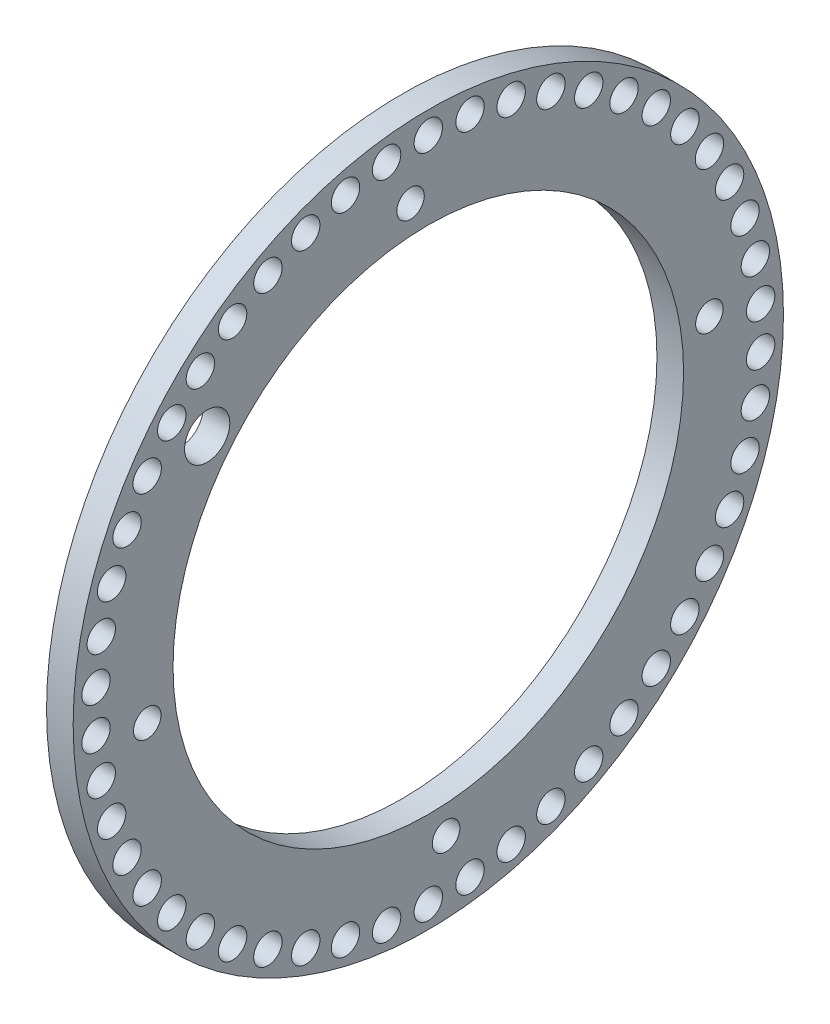
SolidWorks part; units mm, degrees
material "AISI 304"
ref_plane "Front Plane" through (0, 0, 0) normal (0, 0, 1) x (1, 0, 0)
ref_plane "Top Plane" through (0, 0, 0) normal (0, 1, 0) x (1, 0, 0)
ref_plane "Right Plane" through (0, 0, 0) normal (1, 0, 0) x (0, 0, -1)
sketch "Sketch1" plane through (0, 0, 0) normal (1, 0, 0) x (0, 0, -1)
  line L0 (0, 0) -> (0, 40) construction
  line L66 (0, 0) -> (40, 0) construction
  line L67 (0, 0) -> (-40, 0) construction
  line L72 (0, 0) -> (0, -40) construction
  line L73 (0, 0) -> (-28.8942, 23.9034) construction
  line L74 (-22.1523, 18.3259) -> (-19.9302, 21.0119) construction
  line L76 (-27.6614, 22.8835) -> (-26.156, 24.7033) construction
  circle A3 centre (0, 0) radius 40
  circle A24 centre (0, 37.5) radius 1.6
  circle A25 centre (0, 0) radius 28.75
  circle A26 centre (4.7, 37.2043) radius 1.6
  circle A27 centre (9.3259, 36.3219) radius 1.6
  circle A28 centre (13.8047, 34.8666) radius 1.6
  circle A29 centre (18.0658, 32.8615) radius 1.6
  circle A30 centre (22.0419, 30.3381) radius 1.6
  circle A31 centre (25.6705, 27.3363) radius 1.6
  circle A32 centre (28.8942, 23.9034) radius 1.6
  circle A33 centre (31.6623, 20.0935) radius 1.6
  circle A34 centre (33.931, 15.9667) radius 1.6
  circle A35 centre (35.6646, 11.5881) radius 1.6
  circle A36 centre (36.8358, 7.0268) radius 1.6
  circle A37 centre (37.426, 2.3546) radius 1.6
  circle A38 centre (37.426, -2.3546) radius 1.6
  circle A39 centre (36.8358, -7.0268) radius 1.6
  circle A40 centre (35.6646, -11.5881) radius 1.6
  circle A41 centre (33.931, -15.9667) radius 1.6
  circle A42 centre (31.6623, -20.0935) radius 1.6
  circle A43 centre (28.8942, -23.9034) radius 1.6
  circle A44 centre (25.6705, -27.3363) radius 1.6
  circle A45 centre (22.0419, -30.3381) radius 1.6
  circle A46 centre (18.0658, -32.8615) radius 1.6
  circle A47 centre (13.8047, -34.8666) radius 1.6
  circle A48 centre (9.3259, -36.3219) radius 1.6
  circle A49 centre (4.7, -37.2043) radius 1.6
  circle A50 centre (0, -37.5) radius 1.6
  circle A51 centre (-4.7, -37.2043) radius 1.6
  circle A52 centre (-9.3259, -36.3219) radius 1.6
  circle A53 centre (-13.8047, -34.8666) radius 1.6
  circle A54 centre (-18.0658, -32.8615) radius 1.6
  circle A55 centre (-22.0419, -30.3381) radius 1.6
  circle A56 centre (-25.6705, -27.3363) radius 1.6
  circle A57 centre (-28.8942, -23.9034) radius 1.6
  circle A58 centre (-31.6623, -20.0935) radius 1.6
  circle A59 centre (-33.931, -15.9667) radius 1.6
  circle A60 centre (-35.6646, -11.5881) radius 1.6
  circle A61 centre (-36.8358, -7.0268) radius 1.6
  circle A62 centre (-37.426, -2.3546) radius 1.6
  circle A63 centre (-37.426, 2.3546) radius 1.6
  circle A64 centre (-36.8358, 7.0268) radius 1.6
  circle A65 centre (-35.6646, 11.5881) radius 1.6
  circle A66 centre (-33.931, 15.9667) radius 1.6
  circle A67 centre (-31.6623, 20.0935) radius 1.6
  circle A68 centre (-28.8942, 23.9034) radius 1.6
  circle A69 centre (-25.6705, 27.3363) radius 1.6
  circle A70 centre (-22.0419, 30.3381) radius 1.6
  circle A71 centre (-18.0658, 32.8615) radius 1.6
  circle A72 centre (-13.8047, 34.8666) radius 1.6
  circle A73 centre (-9.3259, 36.3219) radius 1.6
  circle A74 centre (-4.7, 37.2043) radius 1.6
  circle A75 centre (-2.0035, 31.8444) radius 1.55
  circle A76 centre (-31.6557, -3.999) radius 1.55
  circle A77 centre (2.0035, -31.8444) radius 1.55
  circle A78 centre (31.6557, 3.999) radius 1.55
  circle A79 centre (-24.9068, 20.6047) radius 2.55
  point P9 (0, -20)
  point P11 (-20, 0)
  point P29 (20, 0)
  point P75 (0, 0)
  point P93 (0, 0)
  point P95 (0, 0)
  point P117 (0, 0)
  point P129 (-27.6614, 22.8835)
  point P130 (-25.0941, 20.7597)
  dimension "D1" = 50
  dimension "D2" = 80
  dimension "D3" = 57.5
  dimension "D5" = 2.5
  dimension "D10" = 6
  dimension "D4" = 3.2
  dimension "D14" = 3.1
  dimension "D15" = 3.1
  dimension "D16" = 3.1
  dimension "D17" = 3.1
  dimension "D18" = 5.1
  dimension "D6" = 6
  dimension "D7" = 6
  dimension "D8" = 6
  dimension "D9" = 6
  dimension "D12" = 6
  dimension "D13" = 6
  dimension "D11" = 6
  dimension "D19" = 3.575
extrude "Boss-Extrude4" add sketch "Sketch1" along normal blind 3
